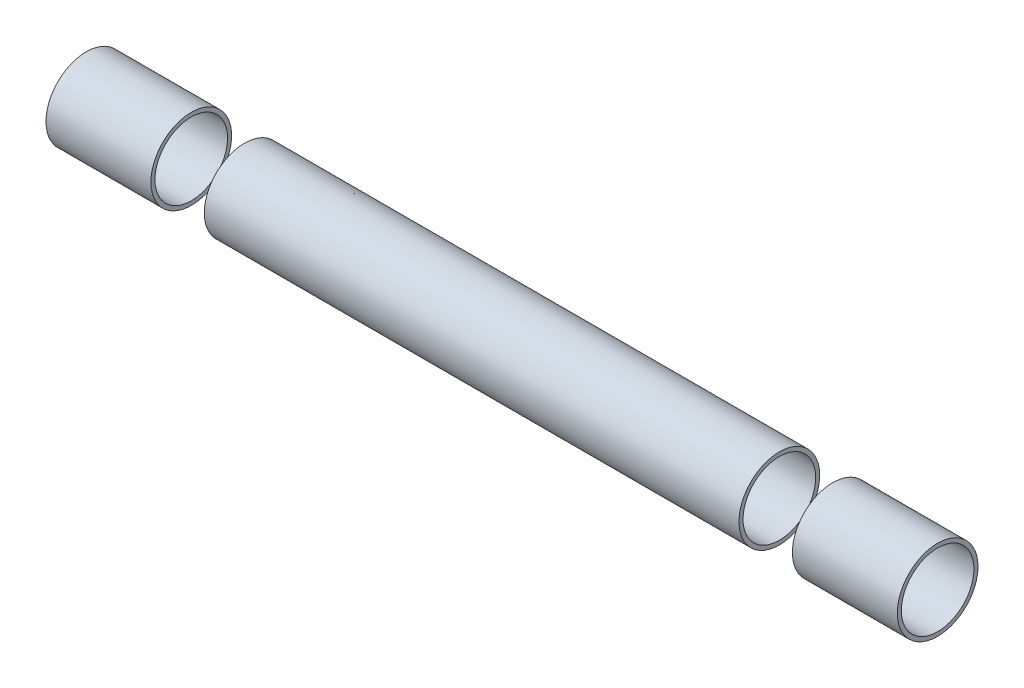
SolidWorks part; units mm, degrees
material "PC High Viscosity"
ref_plane "Front Plane" through (0, 0, 0) normal (0, 0, 1) x (1, 0, 0)
ref_plane "Top Plane" through (0, 0, 0) normal (0, 1, 0) x (1, 0, 0)
ref_plane "Right Plane" through (0, 0, 0) normal (1, 0, 0) x (0, 0, -1)
sketch "Sketch1" plane through (0, 0, 0) normal (1, 0, 0) x (0, 0, -1)
  circle A0 centre (0, 0) radius 15.875
  dimension "D1" = 31.75
extrude "Extrude-Thin1" add sketch "Sketch1" along normal mid plane 334.899 thin thin type one direction reverse wall 1.5875
sketch "Sketch2" plane through (0, 0, 0) normal (0, 0, 1) x (1, 0, 0)
  line L0 (-167.4495, -15.875) -> (167.4495, -15.875) construction
  line L1 (105.1745, -15.875) -> (126.1745, -15.875)
  line L2 (105.1745, -15.875) -> (105.1745, 15.875)
  line L3 (105.1745, 15.875) -> (126.1745, 15.875)
  line L4 (126.1745, -15.875) -> (126.1745, 15.875)
  line L5 (167.4495, 15.875) -> (-167.4495, 15.875) construction
  line L6 (167.4495, -15.875) -> (167.4495, 15.875) construction
  line L7 (0, 0) -> (0, 11.1276) construction
  line L8 (-126.1745, -15.875) -> (-126.1745, 15.875)
  line L9 (-105.1745, 15.875) -> (-126.1745, 15.875)
  line L10 (-105.1745, -15.875) -> (-105.1745, 15.875)
  line L11 (-105.1745, -15.875) -> (-126.1745, -15.875)
  dimension "D1" = 41.275
  dimension "D2" = 21
extrude "Cut-Extrude1" cut sketch "Sketch2" against normal through all both and the other way through all
equation "\"D2@Sketch2\"=21mm"
